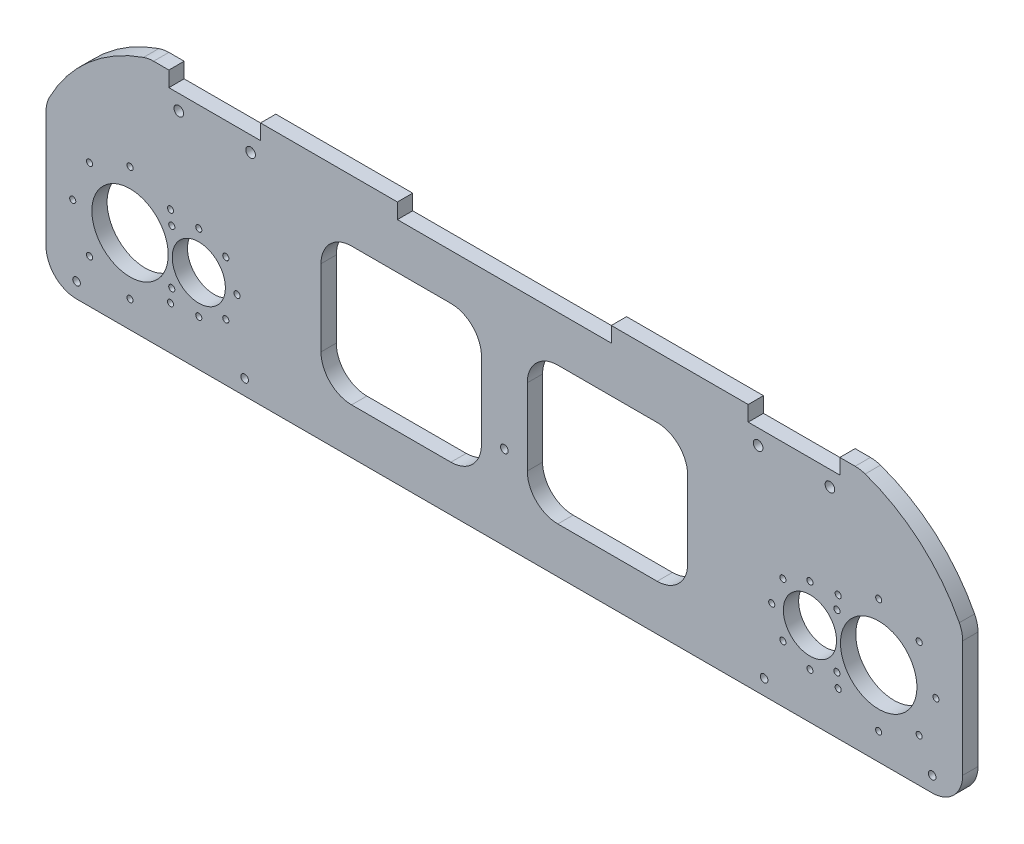
SolidWorks part; units mm, degrees
material "ABS"
ref_plane "Front Plane" through (0, 0, 0) normal (0, 0, 1) x (1, 0, 0)
ref_plane "Top Plane" through (0, 0, 0) normal (0, 1, 0) x (1, 0, 0)
ref_plane "Right Plane" through (0, 0, 0) normal (1, 0, 0) x (0, 0, -1)
sketch "Sketch1" plane through (0, 0, 0) normal (0, 0, 1) x (1, 0, 0)
  line L0 (-145.7836, 66.675) -> (145.7836, 66.675)
  line L1 (-190.5, 26.1817) -> (-190.5, -22.225)
  line L4 (0, 0) -> (0, 100.7987) construction
  line L5 (-177.8, -34.925) -> (177.8, -34.925)
  line L6 (190.5, 26.1817) -> (190.5, -22.225)
  line L7 (-190.5, 34.925) -> (190.5, -34.925) construction
  line L8 (-190.5, -34.925) -> (190.5, 34.925) construction
  arc A0 (177.8, -34.925) -> (190.5, -22.225) centre (177.8, -22.225) ccw
  arc A1 (149.9577, 65.9694) -> (189.0889, 31.9999) centre (127, 0) cw
  circle A2 centre (-127, 0) radius 3.175
  circle A3 centre (127, 0) radius 3.175
  arc A4 (-177.8, -34.925) -> (-190.5, -22.225) centre (-177.8, -22.225) cw
  arc A5 (190.5, 26.1817) -> (189.0889, 31.9999) centre (177.8, 26.1817) ccw
  arc A6 (-149.9577, 65.9694) -> (-189.0889, 31.9999) centre (-127, 0) ccw
  arc A7 (149.9577, 65.9694) -> (145.7836, 66.675) centre (145.7836, 53.975) ccw
  arc A8 (-190.5, 26.1817) -> (-189.0889, 31.9999) centre (-177.8, 26.1817) cw
  arc A9 (-145.7836, 66.675) -> (-149.9577, 65.9694) centre (-145.7836, 53.975) ccw
  point P0 (0, 0)
  point P22 (190.5, 29.0994)
  point P27 (147.8199, 66.675)
  point P30 (-190.5, 29.0994)
  point P33 (-147.8199, 66.675)
  dimension "D3" = 6.35
  dimension "D4" = 6.35
  dimension "D6" = 66.675
  dimension "D7" = 12.7
  dimension "D2" = 381
  dimension "D5" = 12.7
  dimension "D1" = 69.85
  dimension "D8" = 139.7
extrude "Boss-Extrude1" add sketch "Sketch1" along normal mid plane 6.35
sketch "Sketch2" plane through (0, 0, 3.175) normal (0, 0, 1) x (1, 0, 0)
  line L0 (-127, 0) -> (-207.737, 0) construction
  line L4 (0, 0) -> (0, 93.9723) construction
  circle A0 centre (-127, 0) radius 11.049
  circle A1 centre (-155.575, 0) radius 15.875
  circle A2 centre (127, 0) radius 15.875 construction
  circle A3 centre (155.575, 0) radius 23.8125 construction
  circle A4 centre (-155.575, 0) radius 23.8125 construction
  circle A5 centre (-127, 0) radius 15.875 construction
  circle A6 centre (-155.575, 23.8125) radius 1.27
  circle A7 centre (-138.737, 16.838) radius 1.27
  circle A8 centre (-131.7625, 0) radius 1.27 [skipped]
  circle A9 centre (-138.737, -16.838) radius 1.27
  circle A10 centre (-155.575, -23.8125) radius 1.27
  circle A11 centre (-172.413, -16.838) radius 1.27
  circle A12 centre (-179.3875, 0) radius 1.27
  circle A13 centre (-172.413, 16.838) radius 1.27
  circle A14 centre (-127, 15.875) radius 1.27
  circle A15 centre (-115.7747, 11.2253) radius 1.27
  circle A16 centre (-111.125, 0) radius 1.27
  circle A17 centre (-115.7747, -11.2253) radius 1.27
  circle A18 centre (-127, -15.875) radius 1.27
  circle A19 centre (-138.2253, -11.2253) radius 1.27
  circle A20 centre (138.2253, 11.2253) radius 1.27
  circle A21 centre (-138.2253, 11.2253) radius 1.27
  circle A22 centre (-142.875, 0) radius 1.27 [skipped]
  circle A23 centre (138.2253, -11.2253) radius 1.27
  circle A24 centre (127, -15.875) radius 1.27
  circle A25 centre (115.7747, -11.2253) radius 1.27
  circle A26 centre (111.125, 0) radius 1.27
  circle A27 centre (115.7747, 11.2253) radius 1.27
  circle A28 centre (127, 15.875) radius 1.27
  circle A29 centre (172.413, 16.838) radius 1.27
  circle A30 centre (179.3875, 0) radius 1.27
  circle A31 centre (172.413, -16.838) radius 1.27
  circle A32 centre (155.575, -23.8125) radius 1.27
  circle A33 centre (138.737, -16.838) radius 1.27
  circle A34 centre (138.737, 16.838) radius 1.27
  circle A35 centre (155.575, 23.8125) radius 1.27
  circle A36 centre (155.575, 0) radius 15.875
  circle A37 centre (127, 0) radius 11.049
  dimension "D2" = 28.575
  dimension "D3" = 31.75
  dimension "D4" = 31.75
  dimension "D5" = 47.625
  dimension "D6" = 2.54
  dimension "D1" = 22.098
  dimension "D8" = 2.54
  dimension "D7" = 8
  dimension "D9" = 8
extrude "Cut-Extrude1" cut sketch "Sketch2" against normal through all
sketch "Sketch3" plane through (0, 0, 3.175) normal (0, 0, 1) x (1, 0, 0)
  line L0 (0, 0) -> (0, 109.3078) construction
  line L1 (145.7836, 66.675) -> (-145.7836, 66.675) construction
  line L2 (-101.3336, 66.675) -> (-139.4336, 66.675)
  line L3 (-101.3336, 66.675) -> (-101.3336, 60.325)
  line L4 (-101.3336, 60.325) -> (-139.4336, 60.325)
  line L5 (-139.4336, 66.675) -> (-139.4336, 60.325)
  line L6 (139.4336, 66.675) -> (139.4336, 60.325)
  line L7 (101.3336, 60.325) -> (139.4336, 60.325)
  line L8 (101.3336, 66.675) -> (101.3336, 60.325)
  line L9 (101.3336, 66.675) -> (139.4336, 66.675)
  line L11 (44.45, 60.325) -> (-44.45, 60.325)
  line L12 (44.45, 60.325) -> (44.45, 66.675)
  line L13 (44.45, 66.675) -> (-44.45, 66.675)
  line L14 (-44.45, 60.325) -> (-44.45, 66.675)
  line L15 (44.45, 60.325) -> (-44.45, 66.675) construction
  line L16 (44.45, 66.675) -> (-44.45, 60.325) construction
  point P13 (0, 63.5)
  dimension "D1" = 6.35
  dimension "D2" = 38.1
  dimension "D3" = 6.35
  dimension "D4" = 6.35
  dimension "D5" = 88.9
extrude "Cut-Extrude4" cut sketch "Sketch3" against normal through all
sketch "Sketch4" plane through (0, 0, 3.175) normal (0, 0, 1) x (1, 0, 0)
  line L0 (0, 93.6628) -> (0, -75.0769) construction
  line L1 (101.3336, 66.675) -> (44.45, 66.675) construction
  line L2 (-63.5, 41.275) -> (-22.225, 41.275)
  line L3 (-76.2, 28.575) -> (-76.2, -3.175)
  line L4 (-63.5, -15.875) -> (-22.225, -15.875)
  line L5 (76.2, 28.575) -> (76.2, -3.175)
  line L6 (-76.2, 41.275) -> (76.2, -15.875) construction
  line L7 (-76.2, -15.875) -> (76.2, 41.275) construction
  line L8 (-177.8, -34.925) -> (177.8, -34.925) construction
  line L9 (-9.525, 28.575) -> (-9.525, -3.175)
  line L10 (9.525, 28.575) -> (9.525, -3.175)
  line L11 (22.225, 41.275) -> (63.5, 41.275)
  line L12 (22.225, -15.875) -> (63.5, -15.875)
  arc A0 (63.5, 41.275) -> (76.2, 28.575) centre (63.5, 28.575) cw
  arc A1 (76.2, -3.175) -> (63.5, -15.875) centre (63.5, -3.175) cw
  arc A2 (-63.5, -15.875) -> (-76.2, -3.175) centre (-63.5, -3.175) cw
  arc A3 (-63.5, 41.275) -> (-76.2, 28.575) centre (-63.5, 28.575) ccw
  arc A4 (22.225, 41.275) -> (9.525, 28.575) centre (22.225, 28.575) ccw
  arc A5 (22.225, -15.875) -> (9.525, -3.175) centre (22.225, -3.175) cw
  arc A6 (-22.225, -15.875) -> (-9.525, -3.175) centre (-22.225, -3.175) ccw
  arc A7 (-22.225, 41.275) -> (-9.525, 28.575) centre (-22.225, 28.575) cw
  point P2 (0, 12.7)
  point P30 (9.525, 41.275)
  point P33 (9.525, -15.875)
  dimension "D4" = 12.7
  dimension "D7" = 12.7
  dimension "D1" = 25.4
  dimension "D2" = 19.05
  dimension "D3" = 152.4
  dimension "D5" = 9.525
  dimension "D6" = 9.525
extrude "Cut-Extrude5" cut sketch "Sketch4" against normal through all
sketch "Sketch5" plane through (0, 0, 3.175) normal (0, 0, 1) x (1, 0, 0)
  line L0 (-139.4336, 60.325) -> (-101.3336, 60.325) construction
  line L1 (-120.3836, 60.325) -> (-120.3836, 34.1975) construction
  line L2 (0, 75.8339) -> (0, -69.5106) construction
  circle A0 centre (-135.3061, 53.975) radius 2.0035
  circle A1 centre (-105.4611, 53.975) radius 2.0035
  circle A2 centre (105.4611, 53.975) radius 2.0035
  circle A3 centre (135.3061, 53.975) radius 2.0035
  dimension "D1" = 6.35
  dimension "D2" = 14.9225
extrude "Cut-Extrude6" cut sketch "Sketch5" against normal through all
sketch "Sketch6" plane through (0, 0, 3.175) normal (0, 0, 1) x (1, 0, 0)
  line L0 (0, 26.7131) -> (0, -52.4222) construction
  line L1 (-177.8, -34.925) -> (177.8, -34.925) construction
  circle A0 centre (-177.8, -28.575) radius 1.5875
  circle A1 centre (-107.95, -28.575) radius 1.5875
  circle A2 centre (107.95, -28.575) radius 1.5875
  circle A3 centre (177.8, -28.575) radius 1.5875
  dimension "D1" = 3.175
  dimension "D5" = 3.175
  dimension "D2" = 177.8
  dimension "D3" = 6.35
  dimension "D4" = 107.95
extrude "Cut-Extrude7" cut sketch "Sketch6" against normal through all
sketch "Sketch7" plane through (0, 0, 3.175) normal (0, 0, 1) x (1, 0, 0)
  circle A0 centre (0, 0) radius 1.5875
  dimension "D1" = 3.175
extrude "Cut-Extrude8" cut sketch "Sketch7" against normal through all
